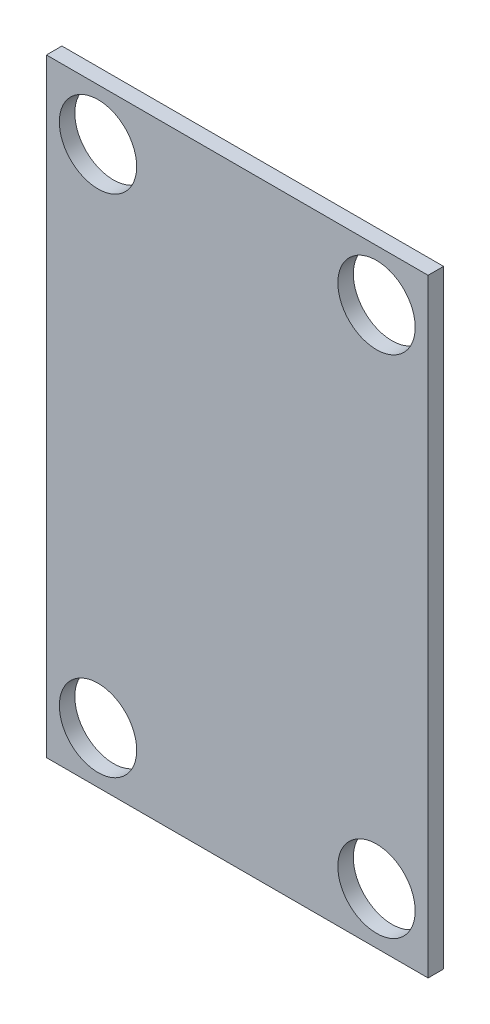
SolidWorks part; units mm, degrees
ref_plane "Спереди" through (0, 0, 0) normal (0, 0, 1) x (1, 0, 0)
ref_plane "Сверху" through (0, 0, 0) normal (0, 1, 0) x (1, 0, 0)
ref_plane "Справа" through (0, 0, 0) normal (1, 0, 0) x (0, 0, -1)
sketch "Эскиз1" plane through (0, 0, 0) normal (0, 0, 1) x (1, 0, 0)
  line L0 (0, -1.5) -> (0, -60.5) construction
  line L1 (-18.5, -1.5) -> (18.5, -1.5)
  line L2 (-18.5, -1.5) -> (-18.5, -60.5)
  line L3 (-18.5, -60.5) -> (18.5, -60.5)
  line L4 (18.5, -1.5) -> (18.5, -60.5)
  line L5 (-18.5, -31) -> (18.5, -31) construction
  circle A1 centre (-13.5, -55.5) radius 3.75
  circle A5 centre (13.5, -55.5) radius 3.75
  circle A6 centre (13.5, -6.5) radius 3.75
  circle A7 centre (-13.5, -6.5) radius 3.75
  dimension "D1" = 27
  dimension "D2" = 27
  dimension "D3" = 49
  dimension "D4" = 49
  dimension "D16" = 7.5
  dimension "D17" = 7.5
  dimension "D18" = 7.5
  dimension "D19" = 7.5
extrude "Бобышка-Вытянуть1" add sketch "Эскиз1" along normal blind 1.5
